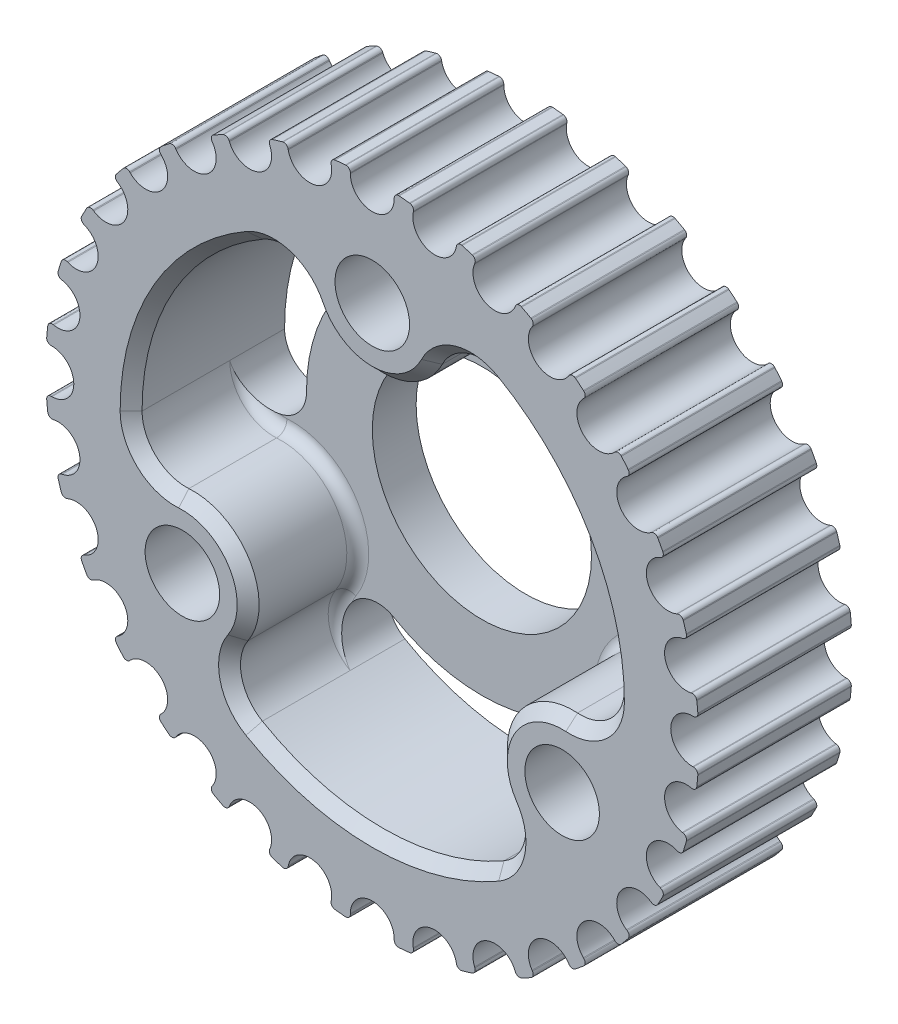
SolidWorks part; units mm, degrees
material "2018 合金"
ref_plane "正面" through (0, 0, 0) normal (0, 0, 1) x (1, 0, 0)
ref_plane "平面" through (0, 0, 0) normal (0, 1, 0) x (1, 0, 0)
ref_plane "右側面" through (0, 0, 0) normal (1, 0, 0) x (0, 0, -1)
sketch "ｽｹｯﾁ1" plane through (0, 0, 0) normal (0, 0, 1) x (1, 0, 0)
  circle A0 centre (0, 0) radius 14.9
  circle A1 centre (0, 0) radius 15.28 construction
  dimension "D1" = 29.8
  dimension "D2" = 30.56
  dimension "D3" = 0.38
extrude "ﾎﾞｽ - 押し出し1" add sketch "ｽｹｯﾁ1" along normal mid plane 7
sketch "ｽｹｯﾁ2" plane through (0, 0, 3.5) normal (0, 0, 1) x (1, 0, 0)
  line L0 (0, 0) -> (0, 16.9223) construction
  line L1 (0, 15.154) -> (0.975, 15.154) construction
  arc A0 (1.2262, 14.8495) -> (-1.2262, 14.8495) centre (0, 0) ccw
  circle A1 centre (0, 0) radius 14.9 construction
  arc A2 (0.3788, 13.7848) -> (-0.3788, 13.7848) centre (0, 0) ccw construction
  arc A3 (-0.9327, 14.6429) -> (-0.4946, 13.8345) centre (0.975, 15.154) ccw
  arc A4 (-0.4946, 13.8345) -> (-0.3788, 13.7848) centre (-0.3829, 13.9347) ccw construction
  arc A5 (-0.9327, 14.6429) -> (-1.2262, 14.8495) centre (-1.2032, 14.5704) ccw
  arc A6 (0.9327, 14.6429) -> (1.2262, 14.8495) centre (1.2032, 14.5704) cw
  arc A7 (0.4946, 13.8345) -> (0.3788, 13.7848) centre (0.3829, 13.9347) cw construction
  arc A8 (0.9327, 14.6429) -> (0.4946, 13.8345) centre (-0.975, 15.154) cw
  arc A9 (-0.4946, 13.8345) -> (0.4946, 13.8345) centre (0, 14.2786) ccw
  point P5 (0, 14.9)
  dimension "D1" = 1.11
  dimension "D4" = 1.975
  dimension "D5" = 0.28
  dimension "D6" = 0.15
  dimension "D2" = 1.95
  dimension "D3" = 0.254
extrude "ｶｯﾄ - 押し出し1" cut sketch "ｽｹｯﾁ2" against normal through all
pattern_circular "円形ﾊﾟﾀｰﾝ1" count 32 over 360 about axis through (0, 0, 3.5) along (0, 0, -1) of "ｶｯﾄ - 押し出し1"
hole_wizard "M3 すきま穴1" positions "ｽｹｯﾁ3" profile "ｽｹｯﾁ4" hole size "M3" standard "JIS" end condition through all
sketch "ｽｹｯﾁ3" plane through (0, 0, 3.5) normal (0, 0, 1) x (1, 0, 0)
  line L0 (0, 10) -> (0, 0) construction
  circle A0 centre (0, 0) radius 10
  point P0 (0, 10)
  dimension "D1" = 20
sketch "ｽｹｯﾁ4" plane through (0, 10, 3.5) normal (1, 0, 0) x (0, -1, 0)
  line L0 (0, 0) -> (0, 7)
  line L1 (0, 7) -> (1.7, 7)
  line L2 (1.7, 7) -> (1.7, 0)
  line L5 (1.7, 0) -> (0, 0)
  line L11 (0, -6.35) -> (0, 107.95) construction
  dimension "通し穴の直径" = 3.4
  dimension "通し穴の深さ" = 7
pattern_circular "円形ﾊﾟﾀｰﾝ2" count 3 over 360 about axis through (0, 0, 3.5) along (0, 0, -1) of "M3 すきま穴1"
sketch "ｽｹｯﾁ5" plane through (0, 0, 3.5) normal (0, 0, 1) x (1, 0, 0)
  line L0 (0, 10) -> (0, 11) construction
  line L1 (-3, 10) -> (-3, 11)
  line L2 (3, 10) -> (3, 11)
  line L3 (8.6603, -5) -> (9.5263, -5.5) construction
  line L4 (10.1603, -2.4019) -> (11.0263, -2.9019)
  line L5 (7.1603, -7.5981) -> (8.0263, -8.0981)
  line L6 (-8.6603, -5) -> (-9.5263, -5.5) construction
  line L7 (-7.1603, -7.5981) -> (-8.0263, -8.0981)
  line L8 (-10.1603, -2.4019) -> (-11.0263, -2.9019)
  circle A0 centre (0, 0) radius 11
  arc A1 (-3, 10) -> (3, 10) centre (0, 10) ccw
  arc A2 (3, 11) -> (-3, 11) centre (0, 11) ccw
  arc A3 (10.1603, -2.4019) -> (7.1603, -7.5981) centre (8.6603, -5) ccw
  arc A4 (8.0263, -8.0981) -> (11.0263, -2.9019) centre (9.5263, -5.5) ccw
  arc A5 (-7.1603, -7.5981) -> (-10.1603, -2.4019) centre (-8.6603, -5) ccw
  arc A6 (-11.0263, -2.9019) -> (-8.0263, -8.0981) centre (-9.5263, -5.5) ccw
  point P6 (0, 10.5)
  point P16 (9.0933, -5.25)
  point P23 (-9.0933, -5.25)
  point P28 (0, 0)
  dimension "D1" = 22
  dimension "D2" = 6
  dimension "D3" = 3
extrude "ｶｯﾄ - 押し出し2" cut sketch "ｽｹｯﾁ5" against normal offset from surface (5 mm away) 2 contours A5 L7 A0 L5 A3 L4 L2 A1 L1 L8 region at (0, 0, 3.5) up to face at (-6.9603, -5, -3.5)
fillet "ﾌｨﾚｯﾄ1" radius 2 6 edges at (-7.6652, -7.8896, 1) (7.6652, -7.8896, 1) (10.6652, -2.6934, 1) (3, 10.583, 1) (-10.6652, -2.6934, 1) (-3, 10.583, 1)
sketch "ｽｹｯﾁ6" plane through (0, 0, -1.5) normal (0, 0, 1) x (1, 0, 0)
  circle A0 centre (0, 0) radius 5
  dimension "D1" = 10
extrude "ｶｯﾄ - 押し出し3" cut sketch "ｽｹｯﾁ6" against normal through all
sketch "ｽｹｯﾁ8" plane through (0, 0, -1.5) normal (0, 0, 1) x (1, 0, 0)
  line L0 (0, 0) -> (4.7394, 8.2333) construction
  line L1 (0, 0) -> (9.5, -0.0122) construction
  arc A0 (4.7394, 8.2333) -> (9.5, -0.0122) centre (0, 0) cw construction
  arc A1 (11, -0.0141) -> (5.4878, 9.5333) centre (0, 0) ccw
  arc A2 (8, -0.0103) -> (3.9911, 6.9333) centre (0, 0) ccw
  arc A3 (8, -0.0103) -> (11, -0.0141) centre (9.5, -0.0122) ccw
  arc A4 (5.4878, 9.5333) -> (3.9911, 6.9333) centre (4.7394, 8.2333) ccw
  point P4 (8.2272, 4.75)
  dimension "D1" = 3
extrude "ｶｯﾄ - 押し出し4" cut sketch "ｽｹｯﾁ8" against normal through all
pattern_circular "円形ﾊﾟﾀｰﾝ3" count 3 over 360 about axis through (0, 0, -3.5) along (0, 0, 1) of "ｶｯﾄ - 押し出し4"
fillet "ﾌｨﾚｯﾄ2" radius 0.5 9 edges at (6.0622, -3.5, -1.5) (-6.0622, -3.5, -1.5) (0, 7, -1.5) (6.4586, -8.2389, -1.5) (10.3644, -1.4739, -1.5) (-10.3644, -1.4739, -1.5) (-6.4586, -8.2389, -1.5) (3.9058, 9.7128, -1.5) (-3.9058, 9.7128, -1.5)
chamfer "面取り1" distance 0.5 angle 45 12 edges at (0, -11, 3.5) (-6.4586, -8.2389, 3.5) (6.4586, -8.2389, 3.5) (-6.0622, -3.5, 3.5) (6.0622, -3.5, 3.5) (-10.3644, -1.4739, 3.5) (10.3644, -1.4739, 3.5) (-9.5263, 5.5, 3.5) (9.5263, 5.5, 3.5) (-3.9058, 9.7128, 3.5) (3.9058, 9.7128, 3.5) (0, 7, 3.5)
sketch "ｽｹｯﾁ12" plane through (0, 0, 3.5) normal (0, 0, 1) x (1, 0, 0)
  line L0 (0, 0) -> (0, 14.6139) construction
  line L1 (0, 14.6139) -> (0, 15.6139) construction
  line L2 (-1, 14.6139) -> (-1, 15.6139)
  line L3 (1, 14.6139) -> (1, 15.6139)
  arc A0 (-1, 14.6139) -> (1, 14.6139) centre (0, 14.6139) ccw
  arc A1 (1, 15.6139) -> (-1, 15.6139) centre (0, 15.6139) ccw
  arc A2 (-0.4946, 13.8345) -> (0.4946, 13.8345) centre (0, 14.2786) ccw construction
  point P3 (0, 15.1139)
  dimension "D1" = 1
  dimension "D2" = 1
extrude "ｶｯﾄ - 押し出し6" cut sketch "ｽｹｯﾁ12" against normal through all
pattern_circular "円形ﾊﾟﾀｰﾝ4" count 32 over 360 about axis through (0, 0, -3.5) along (0, 0, 1) of "ｶｯﾄ - 押し出し6"
fillet "ﾌｨﾚｯﾄ3" radius 0.2 64 edges at (1, 14.7631, 0) (-1, 14.7631, 0) (-11.7195, 9.0334, 0) (-12.8306, 7.3705, 0) (-13.2566, 6.5735, 0) (-14.022, 4.7257, 0) (-14.2843, 3.8609, 0) (-14.6745, 1.8993, 0) (-14.7631, 1, 0) (-14.7631, -1, 0) (-14.6745, -1.8993, 0) (-14.2843, -3.8609, 0) (-14.022, -4.7257, 0) (-13.2566, -6.5735, 0) (-12.8306, -7.3705, 0) (-11.7195, -9.0334, 0) (-11.1462, -9.732, 0) (-9.732, -11.1462, 0) (-9.0334, -11.7195, 0) (-7.3705, -12.8306, 0) (-6.5735, -13.2566, 0) (-4.7257, -14.022, 0) (-3.8609, -14.2843, 0) (-1.8993, -14.6745, 0) (-1, -14.7631, 0) (1, -14.7631, 0) (1.8993, -14.6745, 0) (3.8609, -14.2843, 0) (4.7257, -14.022, 0) (6.5735, -13.2566, 0) (7.3705, -12.8306, 0) (9.0334, -11.7195, 0) (9.732, -11.1462, 0) (11.1462, -9.732, 0) (11.7195, -9.0334, 0) (12.8306, -7.3705, 0) (13.2566, -6.5735, 0) (14.022, -4.7257, 0) (14.2843, -3.8609, 0) (14.6745, -1.8993, 0) (14.7631, -1, 0) (14.7631, 1, 0) (14.6745, 1.8993, 0) (14.2843, 3.8609, 0) (14.022, 4.7257, 0) (13.2566, 6.5735, 0) (12.8306, 7.3705, 0) (11.7195, 9.0334, 0) (11.1462, 9.732, 0) (9.732, 11.1462, 0) (9.0334, 11.7195, 0) (7.3705, 12.8306, 0) (6.5735, 13.2566, 0) (4.7257, 14.022, 0) (3.8609, 14.2843, 0) (1.8993, 14.6745, 0) (-3.8609, 14.2843, 0) (-4.7257, 14.022, 0) (-6.5735, 13.2566, 0) (-7.3705, 12.8306, 0) (-9.0334, 11.7195, 0) (-9.732, 11.1462, 0) (-11.1462, 9.732, 0) (-1.8993, 14.6745, 0)
